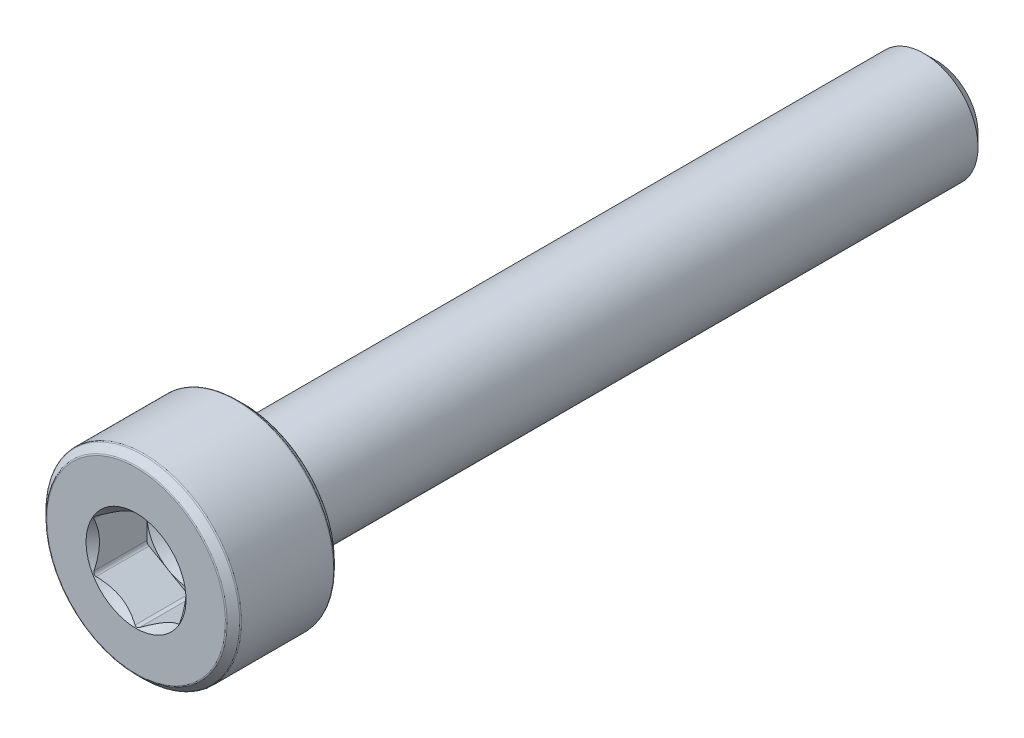
SolidWorks part; units mm, degrees
ref_plane "Front Plane" through (0, 0, 0) normal (0, 0, 1) x (1, 0, 0)
ref_plane "Top Plane" through (0, 0, 0) normal (0, 1, 0) x (1, 0, 0)
ref_plane "Right Plane" through (0, 0, 0) normal (1, 0, 0) x (0, 0, -1)
sketch "Sketch1" plane through (0, 0, 0) normal (1, 0, 0) x (0, 0, -1)
  line L0 (-9.25, 0) -> (9.25, 0) construction
  line L1 (-9.25, 0) -> (-9.25, 2.25)
  line L2 (-9.25, 2.25) -> (-6.75, 2.25)
  line L3 (-6.75, 2.25) -> (-6.75, 1.25)
  line L4 (-6.75, 1.25) -> (8.9577, 1.25)
  line L5 (9.2219, 1.2987) -> (9.4469, 0.909) construction
  line L6 (9.4469, 0.909) -> (9.6719, 1.2987) construction
  line L7 (9.6719, 1.2987) -> (9.2219, 1.2987) construction
  line L8 (8.9577, 1.25) -> (9.25, 0.9577)
  line L9 (9.25, 0.9577) -> (9.25, 0)
  line L10 (9.25, 1.25) -> (9.6438, 1.25) construction
  line L11 (9.4469, 1.2987) -> (9.4469, 1.25) construction
  line L12 (9.4469, 1.25) -> (9.4469, 0.9577) construction
  line L13 (9.4469, 0.9577) -> (9.4469, 0.909) construction
  line L14 (9.4188, 0.9577) -> (9.475, 0.9577)
  line L15 (9.2359, 1.2744) -> (9.6578, 1.2744)
  line L16 (9.475, 0.9577) -> (9.6578, 1.2744)
  line L17 (9.4188, 0.9577) -> (9.2359, 1.2744)
  line L18 (-9.25, 1) -> (-8, 1)
  line L19 (-8, 1) -> (-8, 0)
  line L20 (7.675, 1.25) -> (7.675, -1.25) construction
  point P20 (9.4469, 1.2744)
  point P22 (7.675, -1.25)
  point P28 (7.675, 0)
  point P29 (8.9577, -1.25)
  dimension "Head Diameter" = 4.5
  dimension "Length" = 16
  dimension "Head Height" = 2.5
  dimension "Thread Size" = 2.5
  dimension "D1" = 45
  dimension "Thread Pitch" = 0.45
  dimension "D3" = 0.0563
  dimension "Drive Size" = 2
  dimension "D4" = 1.575
  dimension "D5" = 1.25
sketch "Sketch3" plane through (0, 0, 0) normal (1, 0, 0) x (0, 0, -1)
  line L0 (-9.25, 2.0638) -> (-9.25, 1)
  line L1 (-9.25, 1) -> (-8, 1)
  line L2 (-8, 1) -> (-8, 0)
  line L3 (-8, 0) -> (9.25, 0)
  line L4 (9.25, 0) -> (9.25, 0.9577)
  line L5 (9.25, 0.9577) -> (8.9577, 1.25)
  line L6 (8.9577, 1.25) -> (-6.75, 1.25)
  line L7 (-6.75, 1.25) -> (-6.75, 2.0638)
  line L8 (-6.9362, 2.25) -> (-9.0638, 2.25)
  line L9 (-9.2376, 2.0936) -> (-9.0936, 2.2376)
  line L11 (-9.25, 2.25) -> (-6.75, 2.25) construction
  line L12 (-6.9064, 2.2376) -> (-6.7624, 2.0936)
  arc A5 (-6.7624, 2.0936) -> (-6.75, 2.0638) centre (-6.7922, 2.0638) cw
  arc A6 (-6.9362, 2.25) -> (-6.9064, 2.2376) centre (-6.9362, 2.2078) cw
  arc A7 (-9.0638, 2.25) -> (-9.0936, 2.2376) centre (-9.0638, 2.2078) ccw
  arc A8 (-9.25, 2.0638) -> (-9.2376, 2.0936) centre (-9.2078, 2.0638) cw
  point P17 (-8, 2.25)
  point P29 (-9.25, 2.0813)
  dimension "D3" = 0.0422
  dimension "D1" = 45
  dimension "D2" = 0.1687
revolve "Revolve1" add sketch "Sketch3" angle 360 about L0
sketch "Sketch4" plane through (0, 0, 9.25) normal (0, 0, 1) x (1, 0, 0)
  line L1 (0, 1.1547) -> (-1, 0.5774)
  line L2 (-1, 0.5774) -> (-1, -0.5774)
  line L3 (-1, -0.5774) -> (0, -1.1547)
  line L4 (0, -1.1547) -> (1, -0.5774)
  line L5 (1, -0.5774) -> (1, 0.5774)
  line L6 (1, 0.5774) -> (0, 1.1547)
  circle A0 centre (0, 0) radius 1 construction
extrude "Cut-Extrude1" cut sketch "Sketch4" against normal up to vertex (1.25 mm away) up to point (0, 1, 8)
sketch "Sketch5" plane through (0, 0, 9.25) normal (0, 0, 1) x (1, 0, 0)
  circle A0 centre (0, 0) radius 1.1547
extrude "Cut-Extrude2" cut sketch "Sketch5" against normal up to next (1.25 mm away) draft 45
sketch "Sketch10" plane through (0, 0, 8) normal (0, 0, 1) x (1, 0, 0)
  line L0 (1, 0.5774) -> (1, -0.5774) construction
  circle A0 centre (0, 0) radius 1
extrude "Cut-Extrude3" cut sketch "Sketch10" against normal through all draft 60
fillet "Fillet1" radius 0.1 6 edges at (-1, 0.5774, 8.625) (0, 1.1547, 8.625) (1, 0.5774, 8.625) (1, -0.5774, 8.625) (0, -1.1547, 8.625) (-1, -0.5774, 8.625)
sketch "Sketch6" plane through (0, 0, -9.25) normal (0, 0, -1) x (-1, 0, 0)
  circle A0 centre (0, 0) radius 1.25 construction
  circle A1 centre (0, 0) radius 1.25
curve "Helix/Spiral1" [suppressed] pitch 0.45 height 16.45 turns 36.5556
sketch "Sketch7" plane through (0, 0, 0) normal (1, 0, 0) x (0, 0, -1)
  line L0 (9.4188, 0.9577) -> (9.475, 0.9577) construction
  line L1 (9.4188, 0.9577) -> (9.2359, 1.2744) construction
  line L2 (9.2359, 1.2744) -> (9.6578, 1.2744) construction
  line L3 (9.475, 0.9577) -> (9.6578, 1.2744) construction
  line L4 (9.4188, 0.9577) -> (9.475, 0.9577)
  line L5 (9.4188, 0.9577) -> (9.2359, 1.2744)
  line L6 (9.2359, 1.2744) -> (9.6578, 1.2744)
  line L7 (9.475, 0.9577) -> (9.6578, 1.2744)
sweep "Cut-Sweep1" [suppressed] cut profiles "Sketch7" path "Helix/Spiral1"
sketch "Sketch11" plane through (0, 0, 0) normal (1, 0, 0) x (0, 0, -1)
  line L0 (-6.75, 1.3625) -> (-6.6375, 1.25) construction
  line L1 (-6.75, 2.25) -> (-6.75, 1.25) construction
  line L2 (-6.75, 1.25) -> (8.9577, 1.25) construction
  line L3 (-6.6375, 1.25) -> (-6.525, 1.25)
  line L4 (-6.525, 1.25) -> (-5.275, 0)
  line L5 (-9.25, 0) -> (9.25, 0) construction
  line L6 (-5.275, 0) -> (-6.75, 0)
  line L7 (-6.75, 0) -> (-6.75, 1.3625) construction
  line L8 (-6.75, 1.3625) -> (-7.4226, 1.3625)
  line L9 (-7.4226, 1.3625) -> (-7.4226, 0)
  line L10 (-7.4226, 0) -> (-6.75, 0)
  arc A0 (-6.6375, 1.25) -> (-6.75, 1.3625) centre (-6.6375, 1.3625) cw
  dimension "D1" = 45
  dimension "D2" = 0.1125
  dimension "D3" = 45
  dimension "D4" = 0.225
revolve "Revolve2" [suppressed] add sketch "Sketch11" angle 360 about L6
equation "\"D3@Sketch1\" = \"Thread Pitch@Sketch1\" / 8"
equation "\"D4@Sketch1\" = \"Thread Pitch@Sketch1\" * 3.5"
equation "\"D3@Helix/Spiral1\" = \"Length@Sketch1\" + \"Thread Pitch@Sketch1\""
equation "\"D4@Helix/Spiral1\" = \"Thread Pitch@Sketch1\""
equation "\"D5@Sketch1\"=\"Head Height@Sketch1\"*0.5"
equation "\"D2@Sketch3\"=\"Head Diameter@Sketch1\" *0.0375"
equation "\"D2@Sketch11\"=\"Thread Pitch@Sketch1\" / 4"
equation "\"D4@Sketch11\"=\"Thread Pitch@Sketch1\"/2"
equation "\"D1@Fillet1\"=\"Drive Size@Sketch1\"*0.05"
equation "\"D1@Fillet1\" = \"Drive Size@Sketch1\" * 0.05"
equation "\"D3@Sketch3\"=\"D2@Sketch3\"*0.25"
